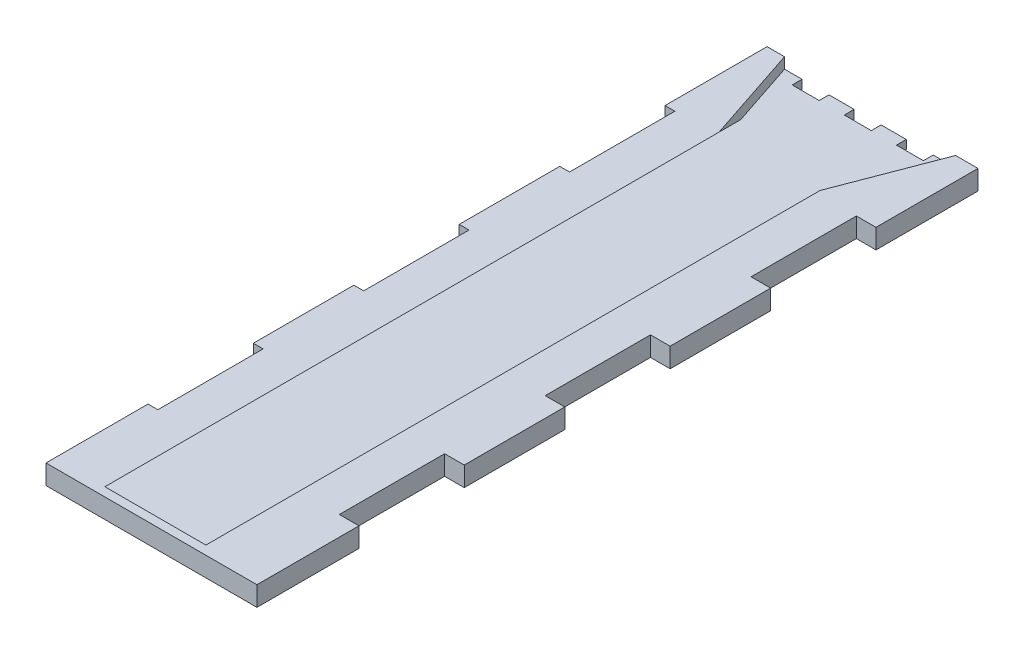
SolidWorks part; units mm, degrees
ref_plane "前视基准面" through (0, 0, 0) normal (0, 0, 1) x (1, 0, 0)
ref_plane "上视基准面" through (0, 0, 0) normal (0, 1, 0) x (1, 0, 0)
ref_plane "右视基准面" through (0, 0, 0) normal (1, 0, 0) x (0, 0, -1)
other "Configuration Table"
sketch "草图4" plane through (0, 0, 0) normal (0, 1, 0) x (1, 0, 0)
  line L6 (-18.5, -72.5) -> (18.5, -72.5)
  line L11 (-18.5, -72.5) -> (-18.5, 72.5)
  line L12 (-18.5, 72.5) -> (18.5, 72.5)
  line L13 (18.5, -72.5) -> (18.5, 72.5)
  line L14 (-18.5, -72.5) -> (18.5, 72.5) construction
  line L15 (-18.5, 72.5) -> (18.5, -72.5) construction
  point P0 (0, 0)
  dimension "D1" = 37
  dimension "D2" = 145
extrude "凸台-拉伸1" add sketch "草图4" along normal blind 4
sketch "草图5" plane through (0, 0, -72.5) normal (0, 0, -1) x (-1, 0, 0)
  line L0 (-18.5, 4) -> (18.5, 4) construction
  line L1 (18.5, 0) -> (13.375, 0)
  line L2 (18.5, 0) -> (18.5, 4)
  line L3 (18.5, 4) -> (13.375, 4)
  line L4 (13.375, 0) -> (13.375, 4)
  line L5 (-18.5, 0) -> (18.5, 0) construction
  line L6 (7.875, 0) -> (2.75, 0)
  line L7 (7.875, 0) -> (7.875, 4)
  line L8 (7.875, 4) -> (2.75, 4)
  line L9 (2.75, 0) -> (2.75, 4)
  line L10 (13.375, 0) -> (7.875, 0)
  line L11 (-2.75, 0) -> (-7.875, 0)
  line L12 (-2.75, 0) -> (-2.75, 4)
  line L13 (-2.75, 4) -> (-7.875, 4)
  line L14 (-7.875, 0) -> (-7.875, 4)
  line L15 (-13.375, 0) -> (-18.5, 0)
  line L16 (-13.375, 0) -> (-13.375, 4)
  line L17 (-13.375, 4) -> (-18.5, 4)
  line L18 (-18.5, 0) -> (-18.5, 4)
  line L19 (2.75, 0) -> (-2.75, 0)
  line L20 (-7.875, 0) -> (-13.375, 0)
  line M17 (-18.5, 0) -> (18.5, 0)
  line M18 (18.5, 0) -> (18.5, 4)
  line M19 (18.5, 4) -> (-18.5, 4)
  line M20 (-18.5, 4) -> (-18.5, 0)
  dimension "D1" = 5.5
extrude "凸台-拉伸2" add sketch "草图5" along normal blind 2 contours L16 M17 M19 M20 | L14 L12 M17 M19 | L9 L7 M17 M19 | L4 M17 M18 M19 region at (-15.9375, 2, -72.5) region at (-5.3125, 2, -72.5) region at (5.3125, 2, -72.5) region at (15.9375, 2, -72.5)
sketch "草图7" plane through (18.5, 0, 0) normal (1, 0, 0) x (0, 0, -1)
  line L0 (-72.5, 4) -> (74.5, 4) construction
  line L1 (-72.5, 0) -> (-51.7, 0)
  line L2 (-72.5, 0) -> (-72.5, 4)
  line L3 (-72.5, 4) -> (-51.7, 4)
  line L4 (-51.7, 0) -> (-51.7, 4)
  line L5 (-72.5, 0) -> (74.5, 0) construction
  line L6 (-30.2333, 0) -> (-9.7333, 0)
  line L7 (-30.2333, 0) -> (-30.2333, 4)
  line L8 (-30.2333, 4) -> (-9.7333, 4)
  line L9 (-9.7333, 0) -> (-9.7333, 4)
  line L10 (-51.7, 2) -> (-30.2333, 2) construction
  line L11 (11.7333, 0) -> (32.2333, 0)
  line L12 (11.7333, 0) -> (11.7333, 4)
  line L13 (11.7333, 4) -> (32.2333, 4)
  line L14 (32.2333, 0) -> (32.2333, 4)
  line L15 (53.7, 0) -> (74.5, 0)
  line L16 (53.7, 0) -> (53.7, 4)
  line L17 (53.7, 4) -> (74.5, 4)
  line L18 (74.5, 0) -> (74.5, 4)
  line L19 (-9.7333, 2) -> (11.7333, 2) construction
  line L20 (32.2333, 2) -> (53.7, 2) construction
  dimension "D1" = 20.8
  dimension "D2" = 20.5
extrude "凸台-拉伸3" add sketch "草图7" along normal blind 4
extrude "凸台-拉伸4" add sketch "草图7<2>" against normal blind 2 from surface starting at face at (-18.5, 2, -1)
sketch "草图7<2>" plane through (18.5, 0, 0) normal (1, 0, 0) x (0, 0, -1) same geometry as "草图7"
sketch "草图8" plane through (0, 0, 72.5) normal (0, 0, 1) x (1, 0, 0)
  line L0 (-10.3, 4) -> (-12.5, 1.8)
  line L1 (-20.5, 4) -> (22.5, 4) construction
  line L3 (12.5, 1.8) -> (10.3, 4)
  line L7 (-10.3, 4) -> (-10.3, 1.8) construction
  line L8 (-10.3, 4) -> (10.3, 4)
  line L9 (0, 0) -> (0, 4) construction
  line L10 (-12.5, 1.8) -> (-10.3, 1.8)
  line L11 (-10.3, 1.8) -> (10.3, 1.8)
  line L12 (10.3, 1.8) -> (12.5, 1.8)
  line L13 (10.3, 4) -> (-10.3, 4)
  line L14 (10.3, 4) -> (10.3, 1.8) construction
  line M13 (22.5, 4) -> (-20.5, 4)
  dimension "D1" = 2.2
  dimension "D2" = 20.6
extrude "切除-拉伸1" cut sketch "草图8" against normal through all from offset 1.8 contours L11 L12 L3 L0 L10 M13 region at (0, 2.8646, 72.5) offset against normal yes
sketch "草图9" plane through (0, 1.8, 0) normal (0, 1, 0) x (1, 0, 0)
  line L0 (-16.9375, 74.5) -> (-10.3, 54.5)
  line L1 (-10.3, 54.5) -> (10.3, 54.5)
  line L2 (10.3, 72.5) -> (10.3, -70.7) construction
  line L3 (10.3, 54.5) -> (17.9375, 74.5)
  line L4 (13.375, 74.5) -> (22.5, 74.5) construction
  line L5 (17.9375, 74.5) -> (-16.9375, 74.5)
  line L6 (-20.5, 74.5) -> (-13.375, 74.5) construction
  line L7 (-10.3, 72.5) -> (-10.3, -70.7) construction
  dimension "D1" = 20
extrude "切除-拉伸2" cut sketch "草图9" along normal through all
